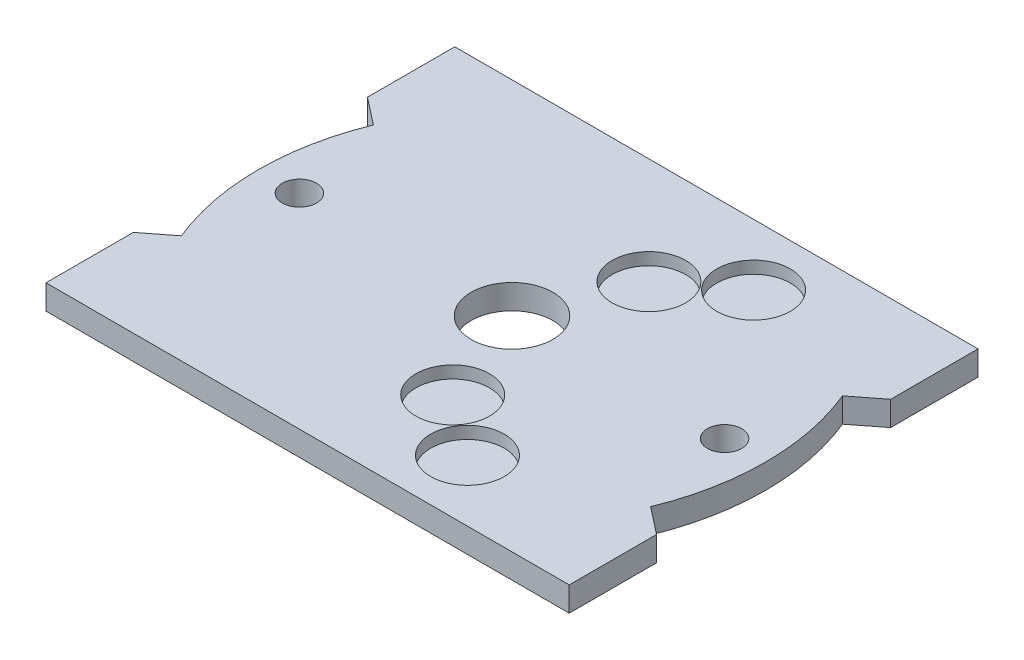
SolidWorks part; units mm, degrees
ref_plane "Front Plane" through (0, 0, 0) normal (0, 0, 1) x (1, 0, 0)
ref_plane "Top Plane" through (0, 0, 0) normal (0, 1, 0) x (1, 0, 0)
ref_plane "Right Plane" through (0, 0, 0) normal (1, 0, 0) x (0, 0, -1)
sketch "Sketch1" plane through (0, 0, 0) normal (0, 1, 0) x (1, 0, 0)
  line L0 (-32, 25) -> (32, -25) construction
  line L1 (32, -25) -> (-32, -25)
  line L2 (32, -25) -> (32, 25)
  line L3 (32, 25) -> (-32, 25)
  line L4 (-32, -25) -> (-32, 25)
  line L5 (0, 25) -> (0, -25) construction
  line L6 (32, 0) -> (-32, 0) construction
  line L7 (-32, -25) -> (32, 25) construction
  line L8 (-18.3303, 25) -> (-11.2626, 19.4783)
  line L9 (-28.6924, 11.7365) -> (-21.6247, 6.2148)
  line L10 (-32, -25) -> (-17.7305, -13.852)
  line L11 (18.3303, 25) -> (11.2626, 19.4783)
  line L12 (-11.2626, -19.4783) -> (-18.3303, -25)
  line L13 (-28.6924, 11.7365) -> (-32, 14.3205)
  line L14 (-21.6247, -6.2148) -> (-32, -14.3205)
  line L15 (28.6924, 11.7365) -> (21.6247, 6.2148)
  line L16 (21.6247, -6.2148) -> (32, -14.3205)
  line L17 (11.2626, -19.4783) -> (18.3303, -25)
  line L18 (28.6924, 11.7365) -> (32, 14.3205)
  line L19 (15.2315, 27) -> (15.2315, 25)
  line L20 (34, -27) -> (-34, -27)
  line L21 (34, -27) -> (34, 27)
  line L22 (34, 27) -> (-34, 27)
  line L23 (-34, -27) -> (-34, 27)
  line L24 (0, 27) -> (0, -27) construction
  line L25 (34, 0) -> (-34, 0) construction
  line L26 (15.2315, 25) -> (32, 25)
  line L27 (32, 14.3205) -> (34, 14.3205)
  line L28 (34, 14.3205) -> (34, 27)
  line L29 (-32, 14.3205) -> (-34, 14.3205)
  line L30 (-15.2315, 27) -> (-15.2315, 25)
  line L31 (32, -14.3205) -> (34, -14.3205)
  line L32 (15.2315, -27) -> (15.2315, -25)
  line L33 (-15.2315, -27) -> (-15.2315, -25)
  line L34 (-32, -14.3205) -> (-34, -14.3205)
  circle A0 centre (0, 0) radius 22.5
  arc A1 (-18.3303, 25) -> (-18.3303, -25) centre (0, 0) ccw
  circle A2 centre (-26, 0) radius 2.1
  circle A3 centre (26, 0) radius 2.1
  arc A4 (18.3303, -25) -> (18.3303, 25) centre (0, 0) ccw
  circle A5 centre (0, 0) radius 5
  point P33 (15.2315, 27)
  dimension "D1" = 45
  dimension "D2" = 62
  dimension "D5" = 4.2
  dimension "D9" = 10
  dimension "D3" = 64
  dimension "D4" = 50
  dimension "D6" = 26
  dimension "D7" = 68
  dimension "D8" = 54
extrude "Boss-Extrude2" add sketch "Sketch1" along normal blind 3 contours A1 L3 L4 L13 | L8 A1 L9 A0 | A0 L11 L3 L8 | L15 A4 L11 A0 | A4 L18 L2 L3 | L16 A4 L15 A0 A3 | L14 A1 L10 A0 | L9 A1 L14 A0 A2 | A1 L14 L4 L10 | A1 L10 L1 | L10 A1 L12 A0 | A0 L12 L1 L17 | L17 A4 L16 A0 | A4 L1 L2 L16 | A0 region at (27.5253, 0, 20.1834) region at (0, 0, 23.1509) region at (20.7114, 0, 16.1808) region at (25.3141, 0, 8.7765) region at (27.5253, 0, -20.1834) region at (-18.0979, 0, 19.5261) region at (20.7114, 0, -16.1808) region at (-25.0676, 0, 23.0669) region at (-23.325, 0, 12.8355) region at (0, 0, -23.1509) region at (-29.2139, 0, 18.2023) region at (-25.3141, 0, 8.7765) region at (-20.7114, 0, -16.1808) region at (-27.5253, 0, -20.1834)
extrude "Cut-Extrude2" cut sketch "Sketch1<14>" along normal blind 10 contours A5
sketch "Sketch1<14>" plane through (0, 0, 0) normal (0, 1, 0) x (1, 0, 0) same geometry as "Sketch1"
sketch "Sketch2" plane through (0, 3, 0) normal (0, 1, 0) x (1, 0, 0)
  line L0 (-26, 0) -> (26, 0) construction
  line L1 (8, 0) -> (8, 11.2082) construction
  line L2 (8.8, 0) -> (8.8, 11.2082) construction
  line L3 (8, 11.2082) -> (8, 12) construction
  line L4 (8, 12) -> (4.75, 12) construction
  line L5 (8.8, 11.2082) -> (8.8, 23.5) construction
  line L6 (8, 0) -> (8, -21.7165) construction
  line L7 (8.8, 0) -> (8.8, -22.7195)
  line L8 (16.3, -22) -> (16.3, -25)
  line L9 (16.3, 22) -> (1.3, 22)
  line L10 (-32, -25) -> (32, -25)
  line L11 (32, -25) -> (32, -14.3205)
  line L12 (32, -14.3205) -> (28.6924, -11.7365)
  line L13 (28.6924, 11.7365) -> (32, 14.3205)
  line L14 (32, 14.3205) -> (32, 25)
  line L15 (32, 25) -> (-32, 25)
  line L16 (-32, 25) -> (-32, 14.3205)
  line L17 (-32, 14.3205) -> (-28.6924, 11.7365)
  line L18 (-28.6924, -11.7365) -> (-32, -14.3205)
  line L19 (-32, -14.3205) -> (-32, -25)
  line L20 (-32, -25) -> (32, -25)
  line L21 (32, -25) -> (32, -14.3205)
  line L22 (32, -14.3205) -> (28.6924, -11.7365)
  line L23 (28.6924, 11.7365) -> (32, 14.3205)
  line L24 (32, 14.3205) -> (32, 25)
  line L25 (32, 25) -> (-32, 25)
  line L26 (-32, 25) -> (-32, 14.3205)
  line L27 (-32, 14.3205) -> (-28.6924, 11.7365)
  line L28 (-28.6924, -11.7365) -> (-32, -14.3205)
  line L29 (-32, -14.3205) -> (-32, -25)
  line L30 (16.3, 22) -> (16.3, 25)
  line L31 (16.3, 25) -> (1.3, 25)
  line L32 (1.3, 22) -> (1.3, 25)
  line L33 (8.8, 25) -> (8.8, 22) construction
  line L34 (16.3, 23.5) -> (1.3, 23.5) construction
  line L35 (16.3, -22) -> (1.3, -22)
  line L36 (1.3, -22) -> (1.3, -25)
  line L37 (8.8, -25) -> (8.8, -22) construction
  circle A0 centre (-26, 0) radius 2.1 construction
  circle A1 centre (-26, 0) radius 2.1
  arc A2 (28.6924, -11.7365) -> (28.6924, 11.7365) centre (0, 0) ccw
  arc A3 (-28.6924, 11.7365) -> (-28.6924, -11.7365) centre (0, 0) ccw
  arc A4 (28.6924, -11.7365) -> (28.6924, 11.7365) centre (0, 0) ccw
  arc A5 (-28.6924, 11.7365) -> (-28.6924, -11.7365) centre (0, 0) ccw
  circle A6 centre (0, 0) radius 5 construction
  circle A7 centre (0, 0) radius 5
  circle A8 centre (26, 0) radius 2.1 construction
  circle A9 centre (26, 0) radius 2.1
  circle A10 centre (0, 0) radius 8
  circle A11 centre (0, 0) radius 3
  circle A12 centre (19.8, 0) radius 11
  circle A13 centre (19.8, 0) radius 3.5
  circle A14 centre (4.75, 12) radius 3.25
  circle A15 centre (4.75, 12) radius 4.5
  circle A16 centre (12.05, 17.5) radius 4.5
  circle A17 centre (12.05, 17.5) radius 3.25
  circle A18 centre (4.75, -12) radius 3.25
  circle A19 centre (4.75, -12) radius 4.5
  circle A20 centre (12.05, -17.5) radius 4.5
  circle A21 centre (12.05, -17.5) radius 3.25
  point P25 (8, 0)
  point P37 (4.8326, 10.9333)
  point P39 (5.5371, 12)
  dimension "D2" = 16
  dimension "D3" = 6
  dimension "D5" = 22
  dimension "D7" = 7
  dimension "D8" = 6.5
  dimension "D9" = 9
  dimension "D11" = 6.5
  dimension "D13" = 9
  dimension "D4" = 0.8
  dimension "D10" = 12
  dimension "D12" = 17.5
  dimension "D14" = 15
  dimension "D15" = 3
  dimension "D1" = 0
extrude "Cut-Extrude3" cut sketch "Sketch2" against normal blind 1.5 contours A16 | A15 | A19 | A20
